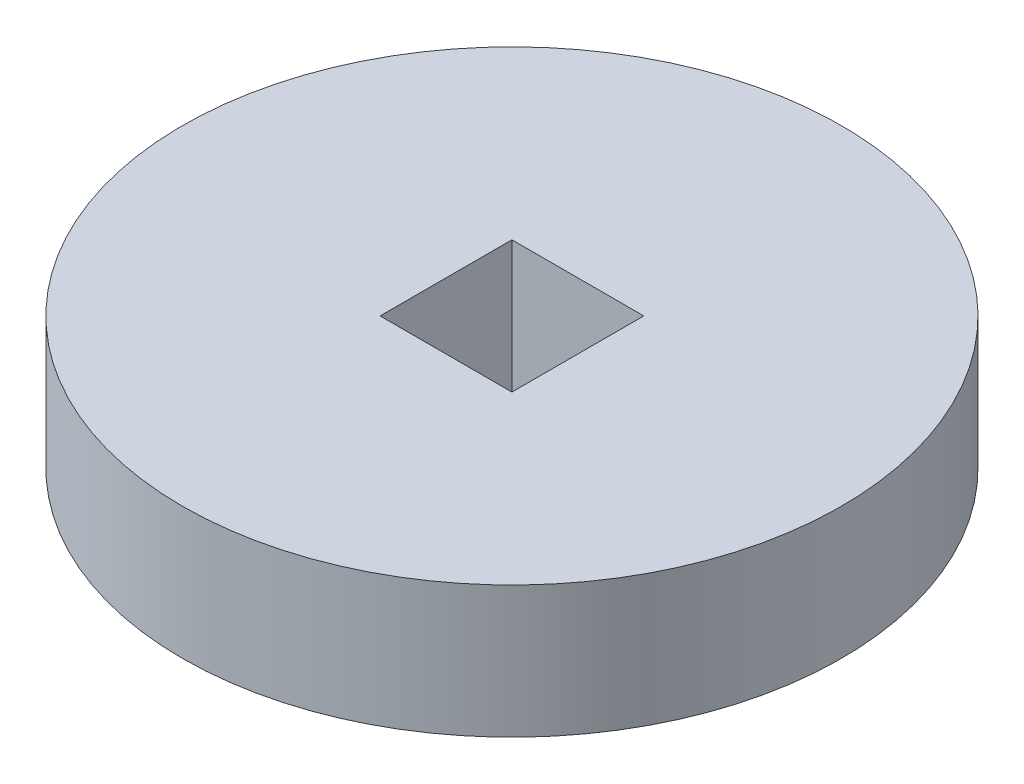
SolidWorks part; units mm, degrees
ref_plane "Front Plane" through (0, 0, 0) normal (0, 0, 1) x (1, 0, 0)
ref_plane "Top Plane" through (0, 0, 0) normal (0, 1, 0) x (1, 0, 0)
ref_plane "Right Plane" through (0, 0, 0) normal (1, 0, 0) x (0, 0, -1)
sketch "Elevator Support Pulleys" plane through (0, 0, 0) normal (0, 1, 0) x (1, 0, 0)
  line L1 (-3.175, 3.175) -> (3.175, 3.175)
  line L2 (-3.175, 3.175) -> (-3.175, -3.175)
  line L3 (-3.175, -3.175) -> (3.175, -3.175)
  line L4 (3.175, 3.175) -> (3.175, -3.175)
  line L5 (-3.175, 3.175) -> (3.175, -3.175) construction
  line L6 (-3.175, -3.175) -> (3.175, 3.175) construction
  circle A0 centre (0, 0) radius 15.875
  dimension "D1" = 31.75
  dimension "D2" = 6.35
  dimension "D3" = 6.35
extrude "Boss-Extrude1" add sketch "Elevator Support Pulleys" along normal blind 6.35
equation "\"Ball Diameter\"= 1.75in"
equation "\"Sheet Thickness\"= 0.25in"
equation "\"Screw Diameter\"= .17in"
equation "\"Robot Diameter\"= 16in"
equation "\"Castor Screw Diameter\"= 0.22in"
equation "\"Wheel Diameter\" = 4in"
equation "\"Nut Diameter\" = 8.4mm"
equation "\"Nut Height\" = 2.9mm"
equation "\"Screw Height\" = 0.55in"
equation "\"Pulley Diameter\" = 1in"
equation "\"Reactor Height\" = 14in"
equation "\"Elevator Height\" = 11.5in"
equation "\"Elevator Width\" = \"Ball Diameter\" + 0.25in"
equation "\"Elevator Axle Length\" = \"Elevator Width\" + 4*\"Sheet Thickness\""
equation "\"D1@Elevator Support Pulleys\"=\"Pulley Diameter\"+0.25in"
equation "\"D2@Elevator Support Pulleys\"=\"Sheet Thickness\""
equation "\"D3@Elevator Support Pulleys\"=\"Sheet Thickness\""
equation "\"D1@Boss-Extrude1\"=\"Sheet Thickness\""
